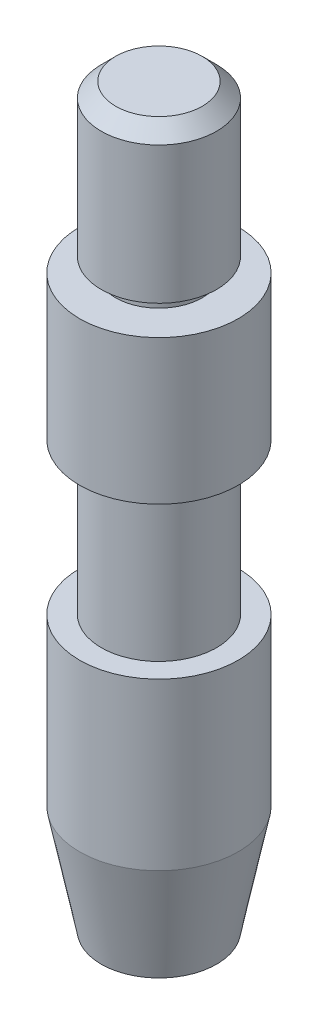
SolidWorks part; units mm, degrees
ref_plane "Plan de face" through (0, 0, 0) normal (0, 0, 1) x (1, 0, 0)
ref_plane "Plan de dessus" through (0, 0, 0) normal (0, 1, 0) x (1, 0, 0)
ref_plane "Plan de droite" through (0, 0, 0) normal (1, 0, 0) x (0, 0, -1)
sketch "Esquisse2" plane through (0, 0, 0) normal (0, 1, 0) x (1, 0, 0)
  circle A0 centre (0, 0) radius 5.5
  dimension "D1" = 11
extrude "Boss.-Extru.2" add sketch "Esquisse2" along normal blind 19 contours A0
chamfer "Chanfrein1" distance 1.5 distance2 7.5 1 edges at (0, 0, 5.5) first distance on face at (0, 0, 5.5)
sketch "Esquisse8" plane through (0, 19, 0) normal (0, 1, 0) x (1, 0, 0)
  circle A0 centre (0, 0) radius 4
  dimension "D1" = 8
extrude "Boss.-Extru.3" add sketch "Esquisse8" along normal blind 10.5
sketch "Esquisse9" plane through (0, 29.5, 0) normal (0, 1, 0) x (1, 0, 0)
  circle A0 centre (0, 0) radius 5.5
  dimension "D1" = 11
extrude "Boss.-Extru.4" add sketch "Esquisse9" along normal blind 10
sketch "Esquisse10" plane through (0, 39.5, 0) normal (0, 1, 0) x (1, 0, 0)
  circle A0 centre (0, 0) radius 3
  dimension "D1" = 6
extrude "Boss.-Extru.5" add sketch "Esquisse10" along normal blind 1
sketch "Esquisse12" plane through (0, 40.5, 0) normal (0, 1, 0) x (1, 0, 0)
  circle A0 centre (0, 0) radius 4
  dimension "D1" = 8
extrude "Boss.-Extru.6" add sketch "Esquisse12" along normal blind 10.5
chamfer "Chanfrein2" distance 1 distance2 1 1 edges at (0, 51, 4)
